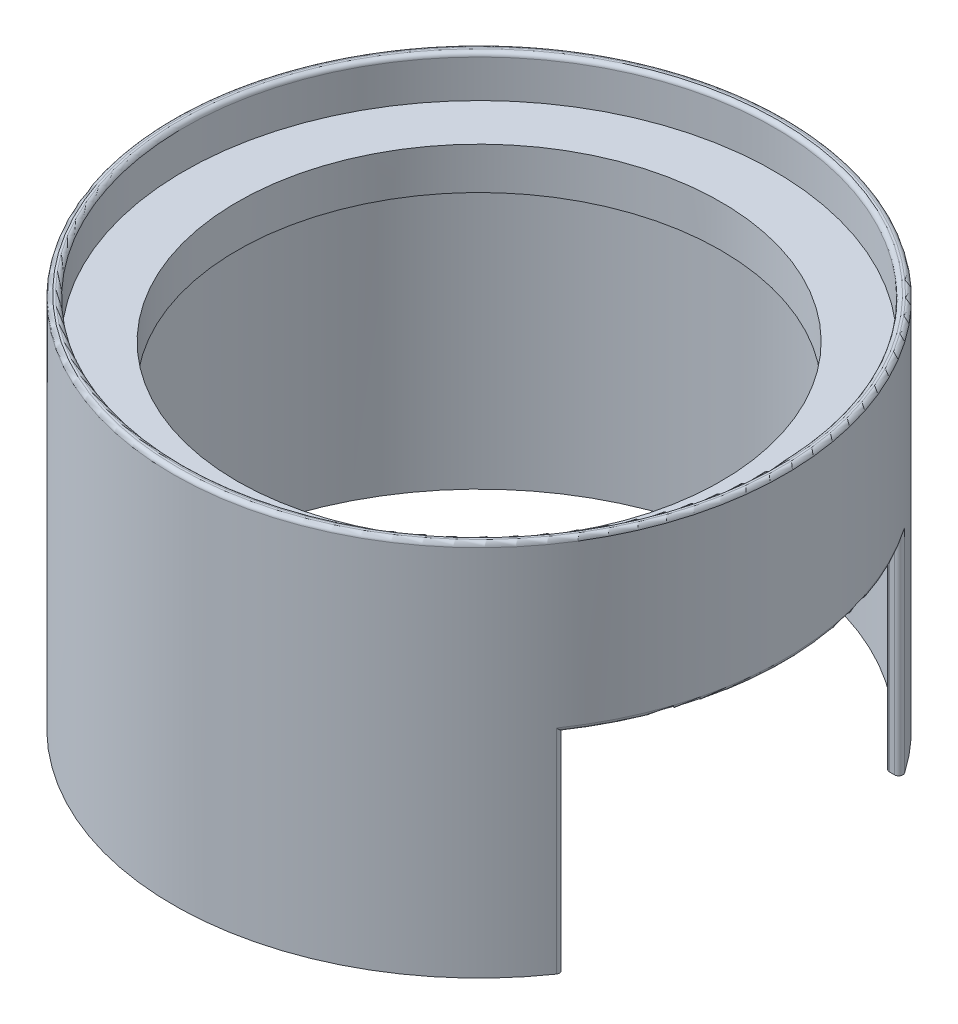
SolidWorks part; units mm, degrees
ref_plane "Front Plane" through (0, 0, 0) normal (0, 0, 1) x (1, 0, 0)
ref_plane "Top Plane" through (0, 0, 0) normal (0, 1, 0) x (1, 0, 0)
ref_plane "Right Plane" through (0, 0, 0) normal (1, 0, 0) x (0, 0, -1)
sketch "Sketch1" plane through (0, 0, 0) normal (0, 1, 0) x (1, 0, 0)
  circle A0 centre (0, 0) radius 7.3
  dimension "D1" = 14.6
extrude "Boss-Extrude1" add sketch "Sketch1" along normal blind 9
sketch "Sketch2" plane through (0, 9, 0) normal (0, 1, 0) x (1, 0, 0)
  circle A0 centre (0, 0) radius 7.05
  dimension "D1" = 14.1
extrude "Cut-Extrude1" cut sketch "Sketch2" against normal blind 1
sketch "Sketch3" plane through (0, 0, 0) normal (0, -1, 0) x (1, 0, 0)
  circle A0 centre (0, 0) radius 7
  dimension "D1" = 14
extrude "Cut-Extrude2" cut sketch "Sketch3" against normal blind 7
sketch "Sketch4" plane through (0, 8, 0) normal (0, 1, 0) x (1, 0, 0)
  circle A0 centre (0, 0) radius 5.775
  dimension "D1" = 11.55
extrude "Cut-Extrude3" cut sketch "Sketch4" against normal through all
ref_plane "Plane1" through (7.3, 0, 0) normal (1, 0, 0) x (0, 0, -1)
sketch "Sketch5" plane through (7.3, 0, 0) normal (1, 0, 0) x (0, 0, -1)
  line L0 (0, 0) -> (0, 9)
  line L1 (7.3, 9) -> (-7.3, 9) construction
  line L2 (-4, 0) -> (4, 0)
  line L3 (8.03, 0) -> (-8.03, 0) construction
  line L4 (-4, 0) -> (-4, 4.9892)
  line L5 (-4, 4.9892) -> (4, 4.9892)
  line L6 (4, 4.9892) -> (4, 0)
  point P9 (0, 0)
  dimension "D1" = 8
  dimension "D2" = 8
extrude "Cut-Extrude4" cut sketch "Sketch5" against normal blind 6 contours L5 L4 L2 L0 | L6 L5 L0 L2 region at (7.3, 2.4946, 2) region at (7.3, 2.4946, -2)
fillet "Fillet7" radius 0.1 2 edges at (0, 9, 7.3) (0, 9, 7.05)
fillet "Fillet9" radius 0.1 3 edges at (6.1066, 2.4946, -4) (7.3, 4.9892, 0) (6.1066, 2.4946, 4)
fillet "Fillet10" radius 0.1 3 edges at (5.7446, 2.4946, -4) (5.7446, 2.4946, 4) (7, 4.9892, 0)
